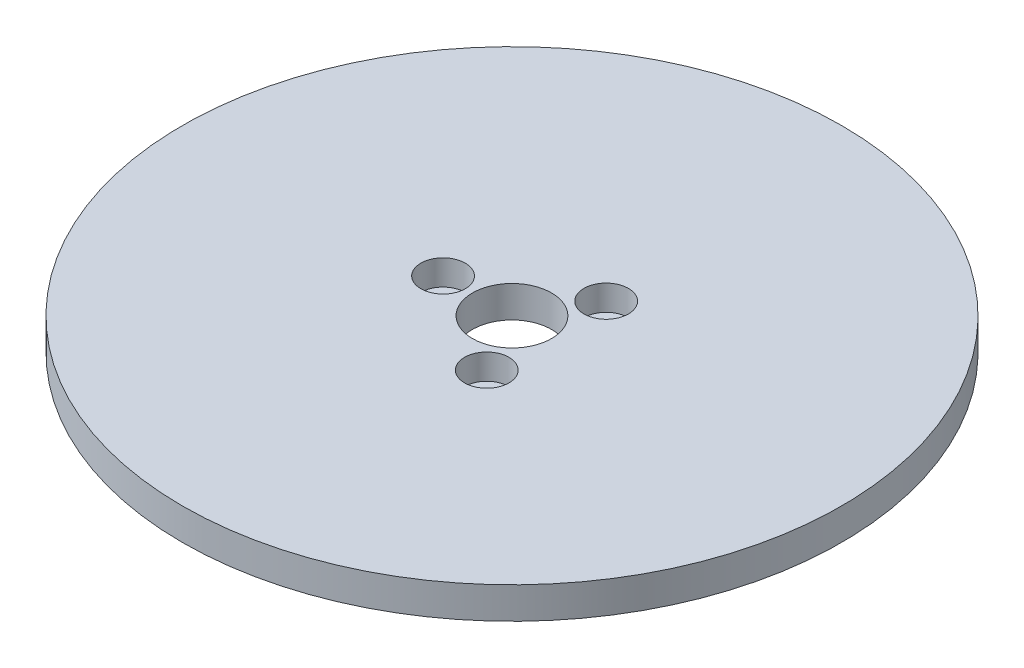
SolidWorks part; units mm, degrees
ref_plane "Front Plane" through (0, 0, 0) normal (0, 0, 1) x (1, 0, 0)
ref_plane "Top Plane" through (0, 0, 0) normal (0, 1, 0) x (1, 0, 0)
ref_plane "Right Plane" through (0, 0, 0) normal (1, 0, 0) x (0, 0, -1)
sketch "Sketch1" plane through (0, 0, 0) normal (0, 1, 0) x (1, 0, 0)
  circle A0 centre (0, 0) radius 62.5
  dimension "FLANGE_OD" = 125
extrude "Boss-Extrude1" add sketch "Sketch1" along normal blind 6
sketch "Sketch2" plane through (0, 0, 0) normal (0, 1, 0) x (1, 0, 0)
  circle A0 centre (0, 0) radius 7.5
  dimension "BORE_D" = 15
extrude "Cut-Extrude1" cut sketch "Sketch2" along normal through all
sketch "Sketch3" plane through (0, 6, 0) normal (0, 1, 0) x (1, 0, 0)
  circle A0 centre (0, 0) radius 13.073 construction
  circle A1 centre (-13.073, 0) radius 4.2131
  dimension "BOLT_D" = 8.4263
  dimension "BOLT_PCD" = 26.146
extrude "Cut-Extrude2" cut sketch "Sketch3" against normal blind 4.8106
pattern_circular "CirPattern1" count 3 over 360 about axis through (0, 0, 0) along (0, 1, 0) of "Cut-Extrude2"
